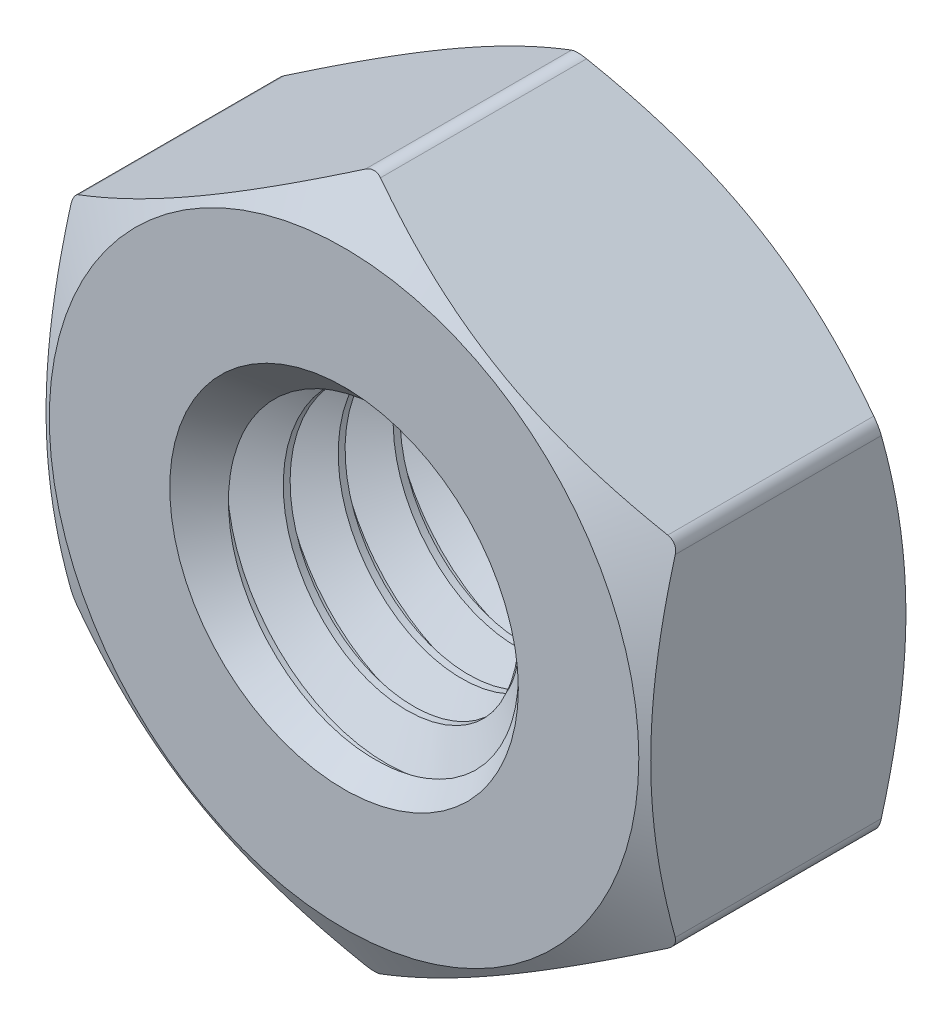
SolidWorks part; units mm, degrees
ref_plane "Front Plane" through (0, 0, 0) normal (0, 0, 1) x (1, 0, 0)
ref_plane "Top Plane" through (0, 0, 0) normal (0, 1, 0) x (1, 0, 0)
ref_plane "Right Plane" through (0, 0, 0) normal (1, 0, 0) x (0, 0, -1)
sketch "Sketch1" plane through (0, 0, 0) normal (1, 0, 0) x (0, 0, -1)
  line L0 (-1.2, 0) -> (1.2, 0) construction
  line L1 (-1.2, -2.75) -> (-1.2, 2.75) construction
  line L2 (1.2, -2.75) -> (1.2, 2.75) construction
  line L3 (-1.2, -1.5) -> (-1.2, 1.5) construction
  line L4 (-1.6688, 1.5541) -> (-1.4188, 1.1211) construction
  line L5 (-1.4188, 1.1211) -> (-1.1688, 1.5541) construction
  line L6 (-1.1688, 1.5541) -> (-1.6688, 1.5541) construction
  line L7 (-1.6531, 1.5271) -> (-1.1844, 1.5271) construction
  line L8 (-1.6375, 1.5) -> (-1.2, 1.5) construction
  line L9 (-1.45, 1.1752) -> (-1.3875, 1.1752) construction
  line L10 (-1.4188, 1.1752) -> (-1.4188, 1.1211) construction
  line L11 (-1.4188, 1.5541) -> (-1.4188, 1.5) construction
  line L12 (-1.2, 1.5854) -> (-1.1146, 1.5) construction
  point P4 (0, 0)
  point P7 (-1.2, 0)
  point P11 (1.2, 0)
  point P14 (-1.2, 0)
  point P26 (-1.4188, 1.5271)
  point P27 (-1.2, -1.5)
  dimension "Height" = 2.4
  dimension "Width" = 5.5
  dimension "Thread Size" = 3
  dimension "D1" = 60
  dimension "Thread Pitch" = 0.5
  dimension "D2" = 0.0625
  dimension "D3" = 45
sketch "Sketch2" plane through (0, 0, 0) normal (0, 0, 1) x (1, 0, 0)
  line L1 (0, 3.1754) -> (-2.75, 1.5877)
  line L2 (-2.75, 1.5877) -> (-2.75, -1.5877)
  line L3 (-2.75, -1.5877) -> (0, -3.1754)
  line L4 (0, -3.1754) -> (2.75, -1.5877)
  line L5 (2.75, -1.5877) -> (2.75, 1.5877)
  line L6 (2.75, 1.5877) -> (0, 3.1754)
  circle A0 centre (0, 0) radius 2.75 construction
  circle A1 centre (0, 0) radius 1.5
extrude "Boss-Extrude1" add sketch "Sketch2" along normal up to vertex (1.2 mm away) and the other way up to vertex (1.2 mm away) up to point (0, -2.75, 1.2) other way up to point (0, -2.75, -1.2)
sketch "Sketch3" plane through (0, 0, 1.2) normal (0, 0, 1) x (1, 0, 0)
  circle A0 centre (0, 0) radius 2.6812
  dimension "D1" = 5.3625
extrude "Cut-Extrude1" cut sketch "Sketch3" against normal through all draft 60 flip side to cut
fillet "Fillet1" radius 0.1375 6 edges at (2.75, -1.5877, -0.1427) (0, -3.1754, -0.1427) (-2.75, -1.5877, -0.1427) (-2.75, 1.5877, -0.1427) (2.75, 1.5877, -0.1427) (0, 3.1754, -0.1427)
sketch "Sketch8" plane through (0, 0, 1.2) normal (0, 0, 1) x (1, 0, 0)
  circle A0 centre (0, 0) radius 1.5854
extrude "Cut-Extrude4" cut sketch "Sketch8" against normal through all draft 45
mirror "Mirror1" about plane through (0, 0, 0) normal (0, 0, 1) of "Cut-Extrude4", "Cut-Extrude1"
sketch "Sketch4" plane through (0, 0, 0) normal (1, 0, 0) x (0, 0, -1)
  line L1 (-1.6531, 1.5271) -> (-1.45, 1.1752)
  line L2 (-1.45, 1.1752) -> (-1.3875, 1.1752)
  line L3 (-1.3875, 1.1752) -> (-1.1844, 1.5271)
  line L4 (-1.6531, 1.5271) -> (-1.1844, 1.5271) construction
  line L5 (-1.6531, 1.5271) -> (-1.1844, 1.5271)
sketch "Sketch5" plane through (0, 0, 1.2) normal (0, 0, 1) x (1, 0, 0)
  circle A0 centre (0, 0) radius 1.5 construction
  circle A1 centre (0, 0) radius 1.5
curve "Helix/Spiral1" pitch 0.5 height 2.9 radius 1.5 centre (0, 0, 1.2) axis (0, 0, -1) start towards (0, 1, 0)
sweep "Sweep1" add profiles "Sketch4" path "Helix/Spiral1"
sketch "Sketch6" plane through (0, 0, 1.2) normal (0, 0, 1) x (1, 0, 0)
  circle A0 centre (0, 0) radius 1.5854 construction
  circle A1 centre (0, 0) radius 1.5854
extrude "Cut-Extrude2" cut sketch "Sketch6" along normal through all and the other way through all draft 45
sketch "Sketch7" plane through (0, 0, -1.2) normal (0, 0, -1) x (-1, 0, 0)
  circle A1 centre (0, 0) radius 1.5854
  circle A2 centre (0, 0) radius 1.5854
  dimension "D1" = 0
extrude "Cut-Extrude3" cut sketch "Sketch7" along normal through all and the other way through all draft 45
equation "\"D2@Sketch1\"=\"Thread Pitch@Sketch1\"/8"
equation "\"D4@Helix/Spiral1\"=\"Thread Pitch@Sketch1\""
equation "\"D3@Helix/Spiral1\"=\"Height@Sketch1\"+\"Thread Pitch@Sketch1\""
equation "\"D1@Sketch3\"=\"Width@Sketch1\"*.975"
equation "\"D1@Fillet1\"=\"Width@Sketch1\"*.025"
